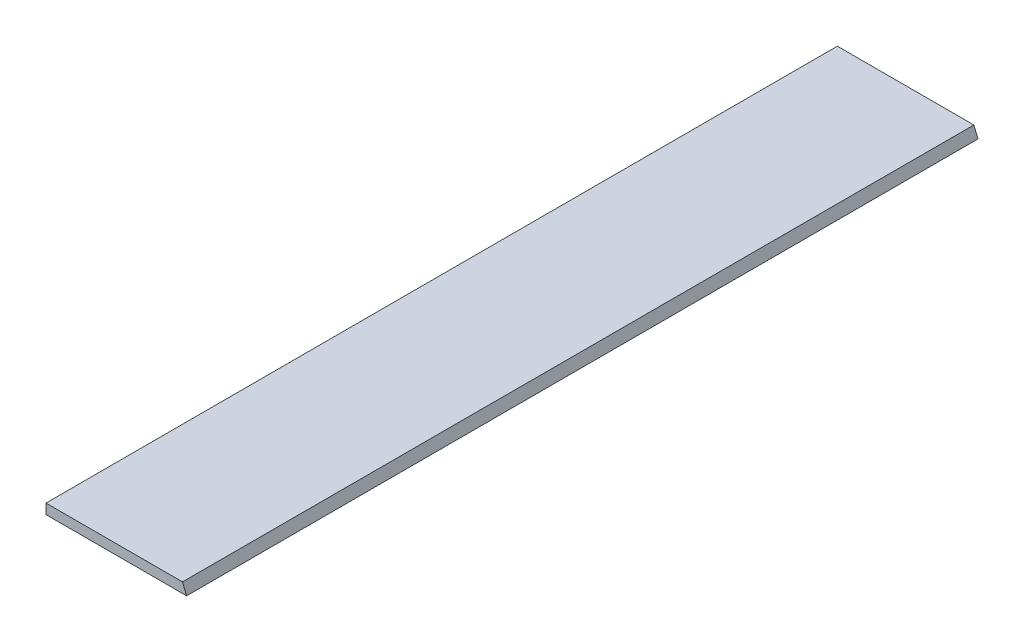
SolidWorks part; units mm, degrees
ref_plane "Front Plane" through (0, 0, 0) normal (0, 0, 1) x (1, 0, 0)
ref_plane "Top Plane" through (0, 0, 0) normal (0, 1, 0) x (1, 0, 0)
ref_plane "Right Plane" through (0, 0, 0) normal (1, 0, 0) x (0, 0, -1)
sketch "Sketch1" plane through (0, 0, 0) normal (0, 0, 1) x (1, 0, 0)
  line L0 (0, 0) -> (0, 6.35)
  line L1 (0, 6.35) -> (86.5237, 6.35)
  line L2 (86.5237, 6.35) -> (89.154, 0)
  line L3 (89.154, 0) -> (0, 0)
  dimension "D1" = 6.35
  dimension "D2" = 67.5
  dimension "D3" = 89.154
extrude "Boss-Extrude1" add sketch "Sketch1" along normal blind 501.65
